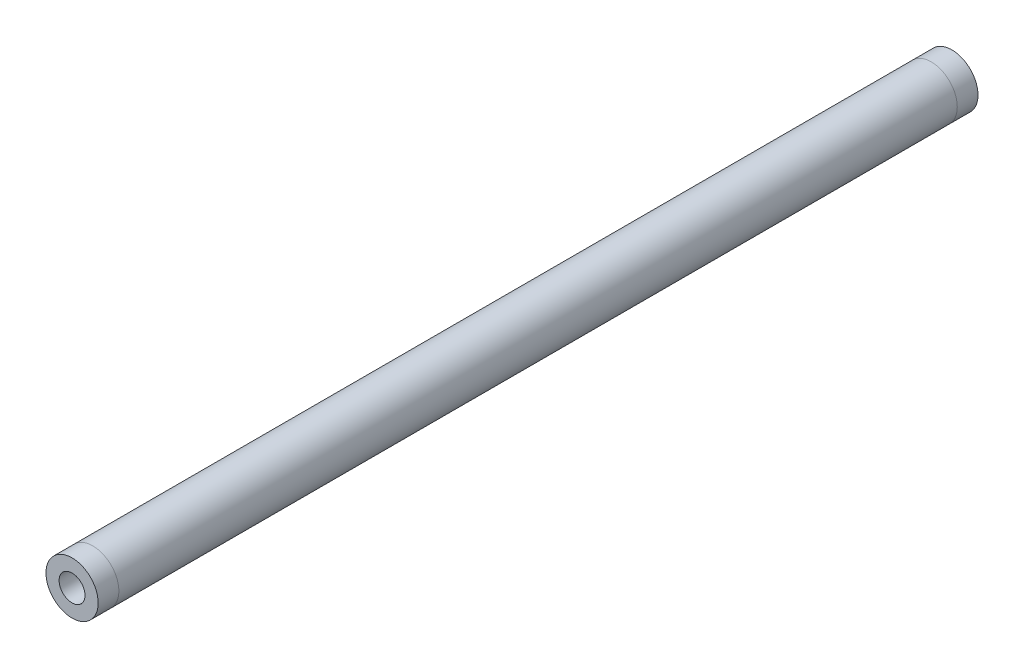
SolidWorks part; units mm, degrees
ref_plane "Front Plane" through (0, 0, 0) normal (0, 0, 1) x (1, 0, 0)
ref_plane "Top Plane" through (0, 0, 0) normal (0, 1, 0) x (1, 0, 0)
ref_plane "Right Plane" through (0, 0, 0) normal (1, 0, 0) x (0, 0, -1)
sketch "Axis" plane through (0, 0, 0) normal (1, 0, 0) x (0, 0, -1)
  line L0 (0, 0) -> (269.654, 0) construction
  line L1 (269.654, 0) -> (263.304, 0)
  line L2 (269.654, 0) -> (304.579, 0) construction
  line L3 (0, 0) -> (-34.925, 0) construction
  point P4 (0, 0)
  point P5 (269.654, 0)
  point P6 (263.304, 0)
  dimension "D1" = 6.35
  dimension "D2" = 34.925
  dimension "D3" = 34.925
sketch "Sketch1" plane through (0, 0, 0) normal (0, 0, 1) x (1, 0, 0)
  circle A0 centre (0, 0) radius 8.001
  circle A1 centre (0, 0) radius 6.477
  circle A2 centre (0, 0) radius 3.9688
  dimension "D1" = 16.002
  dimension "D2" = 1.524
  dimension "D3" = 7.9375
extrude "Threaded insert 1-1" add sketch "Sketch1" against normal blind 6.35 contours A0 A1 | A1 A2 region at (-7.7747, 0, 0) region at (-6.2938, 0, 0)
extrude "Threaded insert 1-2" add sketch "Sketch1<3>" against normal blind 9.525 from surface contours A1 A2 region at (-6.2938, 0, 0) starting at face at (8.001, 0, -6.35)
sketch "Sketch1<3>" plane through (0, 0, 0) normal (0, 0, 1) x (1, 0, 0) same geometry as "Sketch1"
extrude "Tube extrude" add sketch "Sketch1<4>" against normal up to vertex (263.304 mm away) from surface separate body contours A0 A1 region at (-7.7747, 0, 0) up to point (0, 0, -263.304) starting at face at (6.477, 0, -6.35)
sketch "Sketch1<4>" plane through (0, 0, 0) normal (0, 0, 1) x (1, 0, 0) same geometry as "Sketch1"
extrude "Threaded insert 2-1" add sketch "Sketch1<6>" along normal blind 9.525 from surface separate body contours A1 A2 region at (-6.2938, 0, 0) starting at face at (6.477, 0, -263.304)
sketch "Sketch1<6>" plane through (0, 0, 0) normal (0, 0, 1) x (1, 0, 0) same geometry as "Sketch1"
extrude "Threaded insert 2-2" add sketch "Sketch1<9>" against normal blind 6.35 from surface separate body contours A1 A2 | A0 A1 region at (-7.7747, 0, 0) region at (-6.2938, 0, 0) starting at face at (6.477, 0, -263.304)
sketch "Sketch1<9>" plane through (0, 0, 0) normal (0, 0, 1) x (1, 0, 0) same geometry as "Sketch1"
combine bodies "Combine1" operation type add bodies to combine 106 104
equation "\"Threaded insert outer thickness\"= .25"
equation "\"D1@Threaded insert 1-1\"=\"Threaded insert outer thickness\""
equation "\"D1@Threaded insert 2-2\"=\"Threaded insert outer thickness\""
equation "\"D1@Axis\" = \"Threaded insert outer thickness\""
